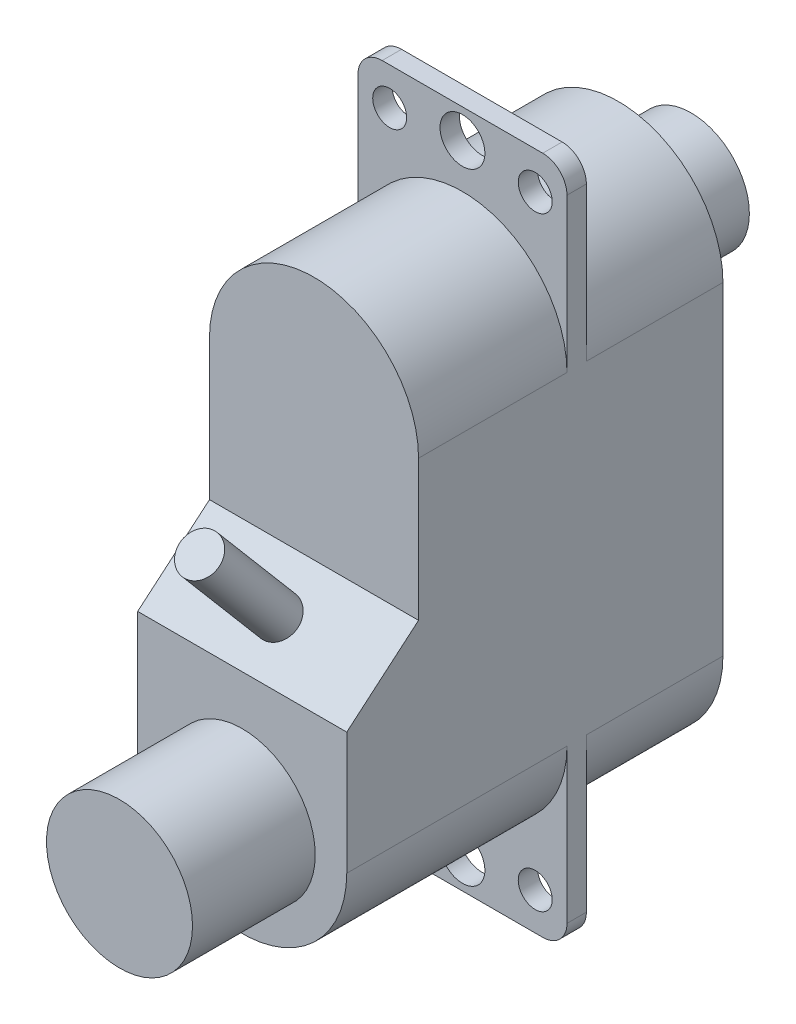
SolidWorks part; units mm, degrees
ref_plane "Front Plane" through (0, 0, 0) normal (0, 0, 1) x (1, 0, 0)
ref_plane "Top Plane" through (0, 0, 0) normal (0, 1, 0) x (1, 0, 0)
ref_plane "Right Plane" through (0, 0, 0) normal (1, 0, 0) x (0, 0, -1)
sketch "Sketch1" plane through (0, 0, 0) normal (0, 0, 1) x (1, 0, 0)
  circle A0 centre (0, 0) radius 2.4
  dimension "D1" = 4.8
extrude "Boss-Extrude1" add sketch "Sketch1" along normal blind 3
sketch "Sketch2" plane through (0, 0, 3) normal (0, 0, 1) x (1, 0, 0)
  line L0 (0, 0) -> (0, -13.34) construction
  line L1 (4.31, 0) -> (4.31, -13.34)
  line L2 (-4.31, 0) -> (-4.31, -13.34)
  line L3 (0, 4.31) -> (12.7239, 4.31) construction
  line L5 (0, -17.65) -> (15.2884, -17.65) construction
  arc A0 (4.31, 0) -> (-4.31, 0) centre (0, 0) ccw
  arc A1 (-4.31, -13.34) -> (4.31, -13.34) centre (0, -13.34) ccw
  point P3 (0, -6.67)
  dimension "D1" = 8.62
  dimension "D2" = 21.96
extrude "Boss-Extrude2" add sketch "Sketch2" along normal blind 15.51
sketch "Sketch3" plane through (0, 0, 0) normal (1, 0, 0) x (0, 0, -1)
  line L0 (-18.51, 4.31) -> (-15.55, 4.31)
  line L1 (-15.55, 4.31) -> (-15.55, -5.79)
  line L2 (-15.55, -5.79) -> (-18.51, -8.3)
  line L3 (-18.51, -13.34) -> (-18.51, 0) construction
  line L4 (-18.51, -8.3) -> (-18.51, 4.31)
  line L5 (-3, 0) -> (-3, 4.31) construction
  dimension "D1" = 12.55
  dimension "D2" = 9.35
  dimension "D3" = 10.1
extrude "Cut-Extrude1" cut sketch "Sketch3" against normal through all both and the other way through all
sketch "Sketch4" plane through (0, 0, 18.51) normal (0, 0, 1) x (1, 0, 0)
  circle A0 centre (0, -13.34) radius 3.01
  dimension "D1" = 6.02
extrude "Boss-Extrude3" add sketch "Sketch4" along normal blind 5.06
ref_plane "Plane1" through (0, 0, 8.63) normal (0, 0, -1) x (-1, 0, 0)
sketch "Sketch5" plane through (0, 0, 8.63) normal (0, 0, -1) x (-1, 0, 0)
  line L1 (-3.31, 7.33) -> (3.31, 7.33)
  line L2 (-4.31, 6.33) -> (-4.31, -19.67)
  line L3 (-3.31, -20.67) -> (3.31, -20.67)
  line L4 (4.31, 6.33) -> (4.31, -19.67)
  line L5 (4.31, 0) -> (4.31, -13.34) construction
  line L6 (0, 0) -> (0, 7.33) construction
  line L8 (4.31, -6.67) -> (10.5668, -6.67) construction
  arc A0 (-4.31, -19.67) -> (-3.31, -20.67) centre (-3.31, -19.67) ccw
  arc A1 (3.31, 7.33) -> (4.31, 6.33) centre (3.31, 6.33) cw
  arc A2 (-3.31, 7.33) -> (-4.31, 6.33) centre (-3.31, 6.33) ccw
  arc A3 (3.31, -20.67) -> (4.31, -19.67) centre (3.31, -19.67) ccw
  circle A4 centre (0, 6.13) radius 0.925
  circle A5 centre (3, 5.7908) radius 0.7
  circle A6 centre (-3, 5.7908) radius 0.7
  circle A7 centre (3, -19.1308) radius 0.7
  circle A8 centre (0, -19.47) radius 0.925
  circle A9 centre (-3, -19.1308) radius 0.7
  point P4 (0, 7.33)
  point P14 (4.31, -6.67)
  point P17 (4.31, -6.67)
  dimension "D1" = 1
  dimension "D2" = 1
  dimension "D4" = 1.85
  dimension "D5" = 1.4
  dimension "D7" = 25.6
  dimension "D3" = 28
  dimension "D6" = 6
extrude "Boss-Extrude4" add sketch "Sketch5" against normal blind 0.8
sketch "Sketch6" plane through (0, 4.3023, 3.6483) normal (0, 0.7627, 0.6468) x (1, 0, 0)
  circle A0 centre (0, -17.5504) radius 0.8231
extrude "Boss-Extrude5" add sketch "Sketch6" along normal blind 5
ref_axis "Axis1" through (0, 0, 8.9133) along (0, 0, -1)
ref_plane "Plane2" through (-4.18, 0.7371, 0) normal (-0.9848, 0.1736, 0) x (0, 0, -1)
ref_plane "Plane3" through (0, 0, 0) normal (0.4226, 0.9063, 0) x (0, 0, -1)
sketch "Sketch7" plane through (0, 0, 8.63) normal (0, 0, -1) x (-1, 0, 0)
  line L8 (2.3137, -18.9928) -> (1.9024, -21.0395)
  line L9 (1.9024, -21.0395) -> (5.9636, -21.0395)
  line L10 (5.9636, -21.0395) -> (5.696, -18.0256)
  line L11 (5.696, -18.0256) -> (2.8529, -18.4464)
  circle A4 centre (3, -19.1308) radius 0.7 construction
  arc A5 (2.8529, -18.4464) -> (2.3137, -18.9928) centre (2.9463, -19.0778) ccw
extrude "Cut-Extrude2" cut sketch "Sketch7" against normal blind 10
